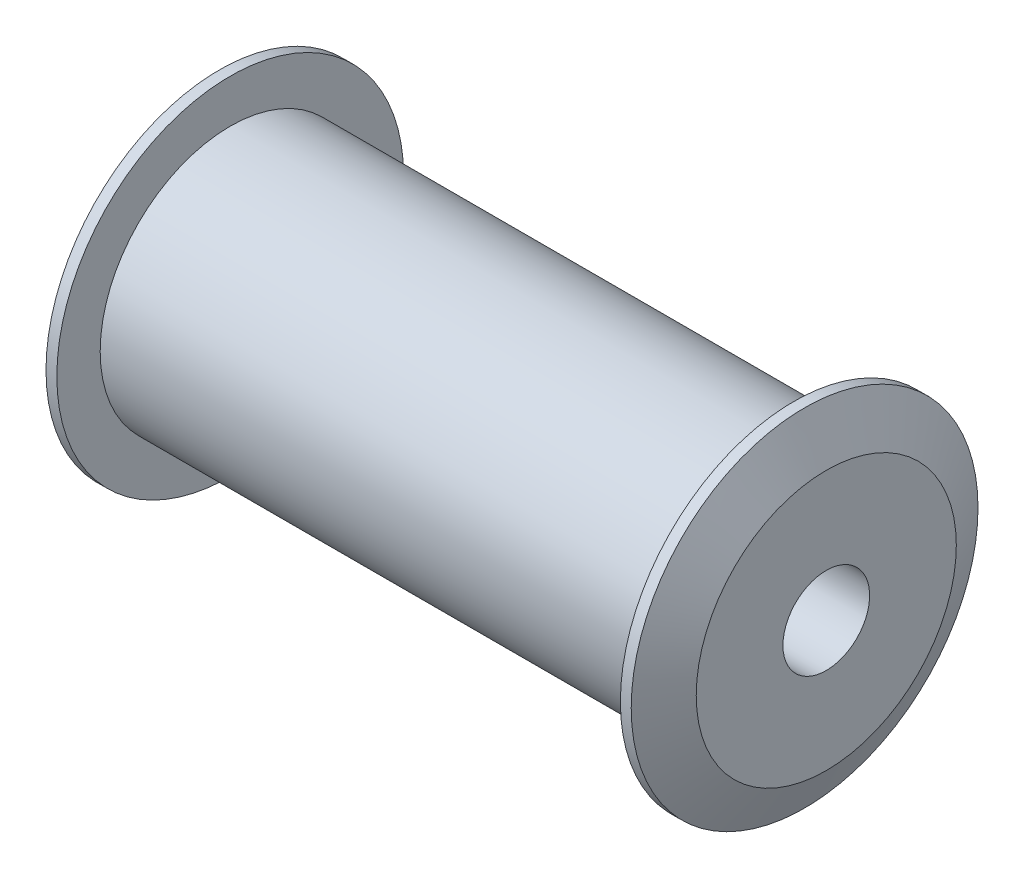
SolidWorks part; units mm, degrees
material "ABS"
ref_plane "前视基准面" through (0, 0, 0) normal (0, 0, 1) x (1, 0, 0)
ref_plane "上视基准面" through (0, 0, 0) normal (0, 1, 0) x (1, 0, 0)
ref_plane "右视基准面" through (0, 0, 0) normal (1, 0, 0) x (0, 0, -1)
sketch "草图2" plane through (0, 0, 0) normal (0, 0, 1) x (1, 0, 0)
  line L0 (-54.7332, 47) -> (96.9258, 47) construction
  line L1 (0, 65.1685) -> (0, 23.0963) construction
  line L2 (-13, 53) -> (13, 53)
  line L3 (-14.5, 55) -> (-14.5, 49)
  line L4 (0, -47.5855) -> (0, 47.5855) construction
  line L5 (14.5, 55) -> (14.5, 49)
  line L6 (-14.5, 55) -> (-13, 55)
  line L7 (-13, 55) -> (-13, 53)
  line L8 (0, -39.5263) -> (0, 39.5263) construction
  line L9 (14.5, 55) -> (13, 55)
  line L10 (13, 55) -> (13, 53)
  line L12 (0, 28.8756) -> (0, 1.3387) construction
  line L13 (-14.5, 49) -> (14.5, 49)
  dimension "D1" = 47
  dimension "D2" = 8
  dimension "D3" = 6
  dimension "D4" = 1.5
  dimension "D5" = 1.5
  dimension "D6" = 2
  dimension "D7" = 29
revolve "旋转1" add sketch "草图2" angle 360 about L0
chamfer "倒角1" distance 1 distance2 2 1 edges at (-14.5, 47, 8) first distance on face at (-14.5, 47, 8)
chamfer "倒角2" distance 2 distance2 1 1 edges at (14.5, 47, 8) first distance on face at (14.5, 47, 8)
